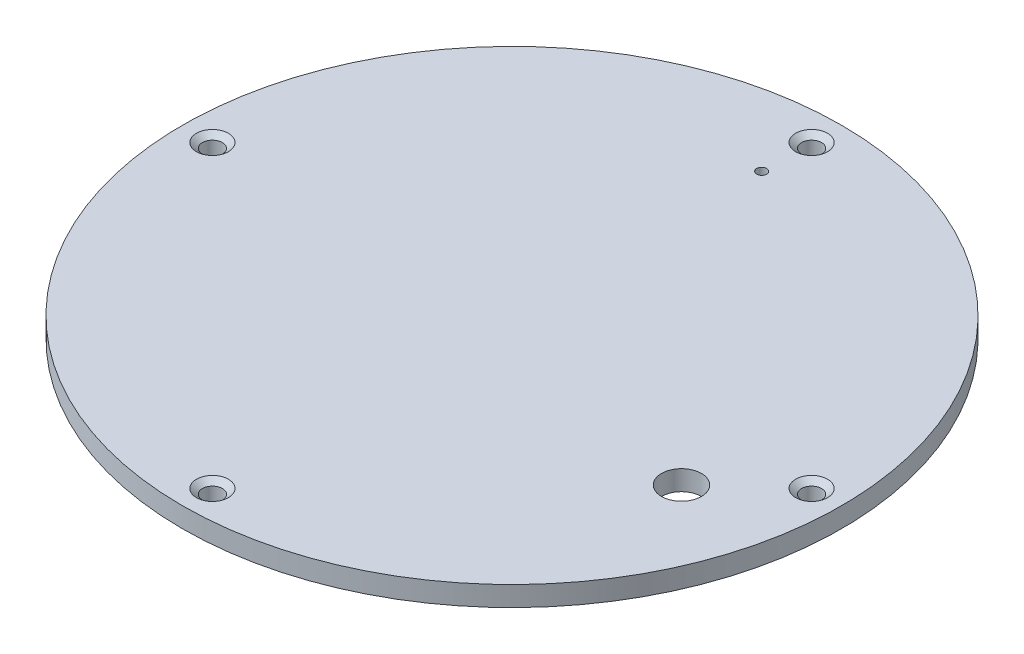
SolidWorks part; units mm, degrees
material "1060 Alloy"
ref_plane "Front Plane" through (0, 0, 0) normal (0, 0, 1) x (1, 0, 0)
ref_plane "Top Plane" through (0, 0, 0) normal (0, 1, 0) x (1, 0, 0)
ref_plane "Right Plane" through (0, 0, 0) normal (1, 0, 0) x (0, 0, -1)
sketch "Sketch1" plane through (0, 0, 0) normal (0, 1, 0) x (1, 0, 0)
  circle A0 centre (0, 0) radius 16.5
  dimension "D1" = 33
extrude "Boss-Extrude1" add sketch "Sketch1" along normal blind 1
sketch "Sketch6" plane through (0, 1, 0) normal (0, 1, 0) x (1, 0, 0)
  line L0 (0, 0) -> (19.3341, -5.1806) construction
  line L1 (0, 0) -> (17.9741, 0) construction
  circle A0 centre (0, 12.5) radius 0.25
  circle A1 centre (11.5911, -3.1058) radius 1
  dimension "D1" = 12.5
  dimension "D3" = 0.5
  dimension "D4" = 2
  dimension "D2" = 0
  dimension "D5" = 12
  dimension "D6" = 15
extrude "Cut-Extrude1" cut sketch "Sketch6" against normal through all both and the other way through all
hole_wizard "CSK for M2 Flat Head Machine Screw1" positions "Sketch7" profile "Sketch8" countersink size "M2" standard "ANSI Metric" end condition through all
sketch "Sketch7" plane through (0, 1, 0) normal (0, 1, 0) x (1, 0, 0)
  point P0 (0, 15)
  point P2 (-15, 0)
  point P4 (0, -15)
  point P6 (15, 0)
  dimension "D1" = 15
  dimension "D2" = 15
  dimension "D3" = 15
  dimension "D4" = 15
sketch "Sketch8" plane through (0, 1, -15) normal (1, 0, 0) x (0, 0, 1)
  line L0 (0, 0) -> (0, 1)
  line L1 (0, 1) -> (0.5, 1)
  line L2 (0.5, 1) -> (0.5, 0.2517)
  line L3 (0.5, 0.2517) -> (0.8, 0)
  line L5 (0.8, 0) -> (0, 0)
  line L6 (-0.5, 0.2517) -> (-0.8, 0) construction
  line L11 (0, -6.35) -> (0, 107.95) construction
  dimension "Thru Hole Dia." = 1
  dimension "Thru Hole Depth" = 1
  dimension "Near C'Sink Dia." = 1.6
  dimension "Near C'Sink Angle" = 100
